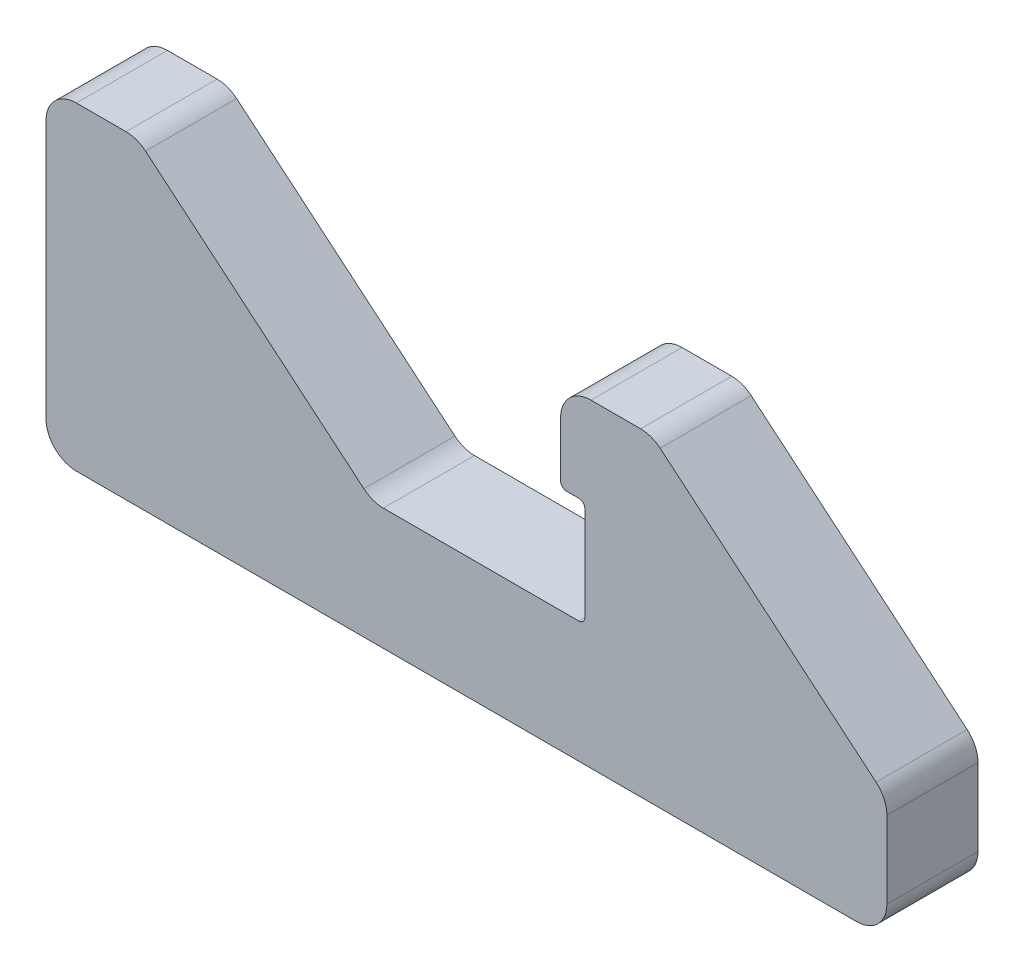
SolidWorks part; units mm, degrees
ref_plane "Front Plane" through (0, 0, 0) normal (0, 0, 1) x (1, 0, 0)
ref_plane "Top Plane" through (0, 0, 0) normal (0, 1, 0) x (1, 0, 0)
ref_plane "Right Plane" through (0, 0, 0) normal (1, 0, 0) x (0, 0, -1)
sketch "Sketch1" plane through (0, 0, 0) normal (0, 0, 1) x (1, 0, 0)
  line L0 (0, 0) -> (0, 105)
  line L1 (0, 105) -> (30, 105)
  line L2 (30, 105) -> (107.464, 40)
  line L3 (107.464, 40) -> (177.464, 40)
  line L4 (177.464, 40) -> (177.464, 75)
  line L5 (177.464, 75) -> (169.464, 75)
  line L6 (169.464, 75) -> (169.464, 105)
  line L7 (169.464, 105) -> (199.464, 105)
  line L8 (199.464, 105) -> (276.928, 40)
  line L9 (276.928, 40) -> (276.928, 0)
  line L10 (276.928, 0) -> (0, 0)
  dimension "D1" = 50
  dimension "D2" = 30
  dimension "D3" = 30
  dimension "D4" = 8
  dimension "D5" = 35
  dimension "D6" = 40
  dimension "D7" = 30
  dimension "D8" = 70
extrude "Boss-Extrude1" add sketch "Sketch1" along normal blind 30
fillet "Fillet1" radius 10 8 edges at (276.928, 0, 15) (0, 0, 15) (0, 105, 15) (30, 105, 15) (107.464, 40, 15) (276.928, 40, 15) (199.464, 105, 15) (169.464, 105, 15)
fillet "Fillet2" radius 2 3 edges at (177.464, 40, 15) (177.464, 75, 15) (169.464, 75, 15)
